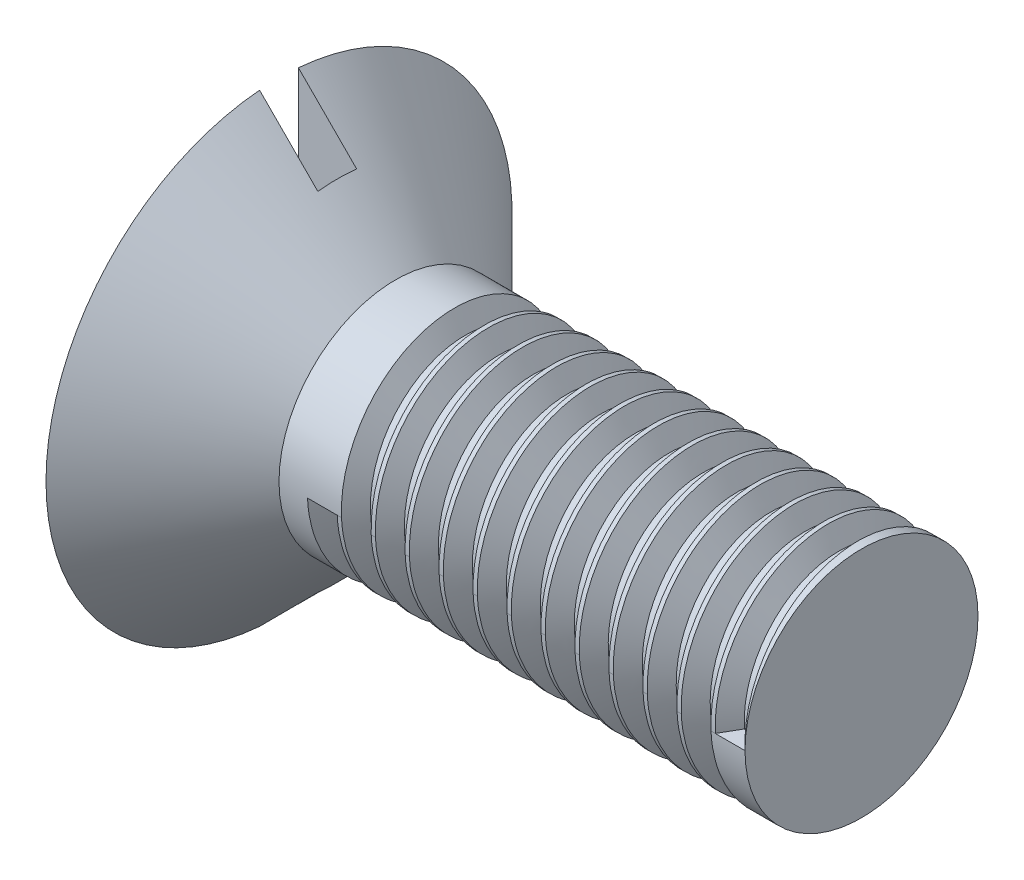
SolidWorks part; units mm, degrees
material "Alloy Steel (SS)"
ref_plane "Front Plane" through (0, 0, 0) normal (0, 0, 1) x (1, 0, 0)
ref_plane "Top Plane" through (0, 0, 0) normal (0, 1, 0) x (1, 0, 0)
ref_plane "Right Plane" through (0, 0, 0) normal (1, 0, 0) x (0, 0, -1)
sketch "Sketch3" plane through (0, 0, 0) normal (0, 0, 1) x (1, 0, 0)
  line L0 (-30, 0) -> (0, 0)
  line L1 (0, 0) -> (0, 6)
  line L2 (0, 6) -> (-24, 6)
  line L3 (-24, 6) -> (-30, 12)
  line L4 (-30, 12) -> (-30, 0)
  dimension "D1" = 30
  dimension "D2" = 6
  dimension "D3" = 12
  dimension "D4" = 45
  dimension "D5" = 6
revolve "Revolve1" add sketch "Sketch3" angle 360 about L0
sketch "Sketch4" plane through (-30, 0, 0) normal (-1, 0, 0) x (0, 0, 1)
  line L0 (0, 17.0209) -> (0, -15.1926) construction
  line L2 (-1, 15.0185) -> (1, 15.0185)
  line L3 (-1, 15.0185) -> (-1, -14.5831)
  line L4 (-1, -14.5831) -> (1, -14.5831)
  line L5 (1, 15.0185) -> (1, -14.5831)
  line L6 (0, -14.5831) -> (0, 15.0185) construction
  line L7 (-1, 0.2177) -> (1, 0.2177) construction
  point P195 (0, 0.2177)
  dimension "D1" = 2
extrude "Cut-Extrude1" cut sketch "Sketch4" against normal blind 3
thread "Thread1" pitch 1.75 method cut profile "Thread Profile1" start angle 0, offset 0, length 21, pitch 1.75, diameter 12
ref_plane "Plane1" through (0, 0, 6) normal (0, -1, 0) x (0, 0, 1)
sketch "Thread Profile1" plane through (0, 0, 6) normal (0, -1, 0) x (0, 0, 1)
  line L0 (0, 0) -> (0, 1.75) construction
  line L11 (0, 0) -> (0, 1.5312)
  line L12 (0, 1.5312) -> (-0.9472, 0.9844)
  line L13 (-0.9472, 0.9844) -> (-0.9472, 0.5469)
  line L15 (-0.9472, 0.5469) -> (0, 0)
  line L17 (-0.9472, 0.7656) -> (0, 0.7656) construction
  point P2 (0, 0)
  dimension "Pitch" = 1.75
  dimension "Profile_Angle" = 60
  dimension "Profile_Land" = 0.4375
  dimension "Profile_Height" = 0.9472
